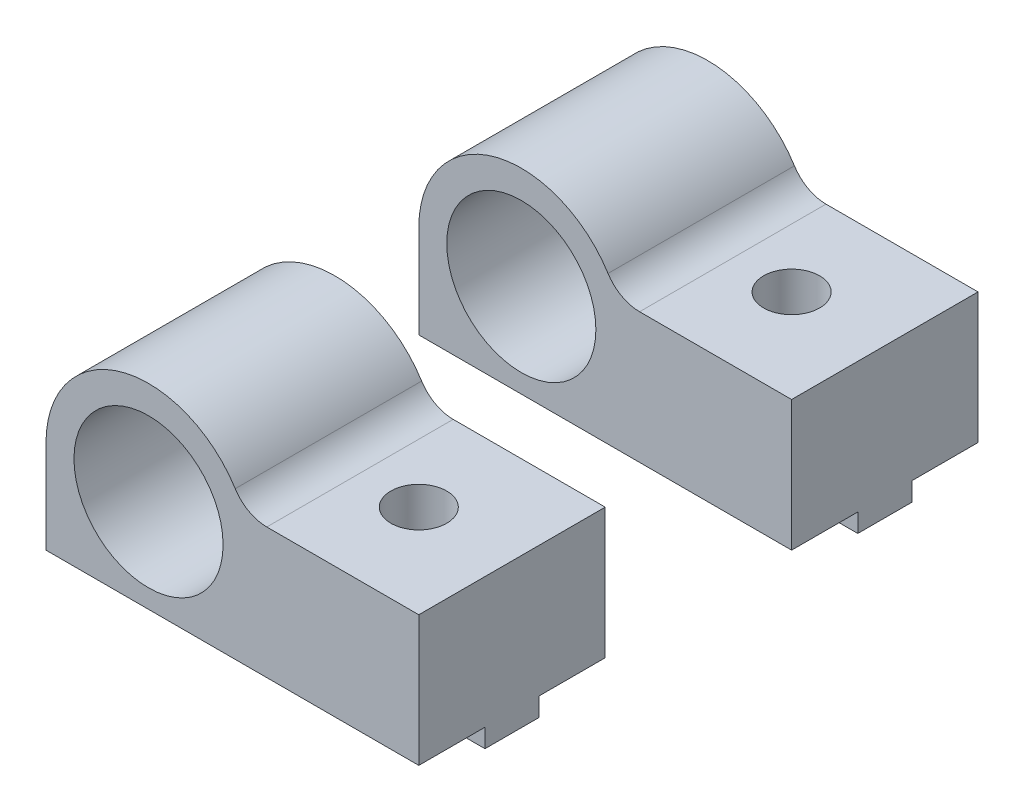
SolidWorks part; units mm, degrees
ref_plane "Front Plane" through (0, 0, 0) normal (0, 0, 1) x (1, 0, 0)
ref_plane "Top Plane" through (0, 0, 0) normal (0, 1, 0) x (1, 0, 0)
ref_plane "Right Plane" through (0, 0, 0) normal (1, 0, 0) x (0, 0, -1)
sketch "Sketch1" plane through (0, 0, 0) normal (0, 0, 1) x (1, 0, 0)
  line L0 (-5.5, 0) -> (-5.5, -5)
  line L1 (14.5, -5) -> (14.5, 2)
  line L3 (-5.5, -5) -> (14.5, -5)
  line L4 (14.5, 2) -> (5.1235, 2)
  arc A0 (-5.5, 0) -> (5.1235, 2) centre (0, 0) cw
  circle A1 centre (0, 0) radius 4
  dimension "D1" = 8
  dimension "D2" = 5.5
  dimension "D3" = 5
  dimension "D4" = 7
  dimension "D5" = 20
  dimension "D6" = 9.3765
extrude "Main" add sketch "Sketch1" along normal blind 10
sketch "Sketch3" plane through (0, -5, 0) normal (0, -1, 0) x (-1, 0, 0)
  line L0 (5.5, -10) -> (5.5, 0) construction
  line L1 (5.5, -6.45) -> (-14.5, -6.45)
  line L2 (5.5, -6.45) -> (5.5, -3.55)
  line L3 (5.5, -3.55) -> (-14.5, -3.55)
  line L4 (-14.5, -6.45) -> (-14.5, -3.55)
  line L5 (-14.5, -10) -> (-14.5, 0) construction
  line L6 (5.5, 0) -> (-14.5, 0) construction
  dimension "D1" = 2.9
  dimension "D2" = 3.55
extrude "MakerBeamRectangularGuide" add sketch "Sketch3" along normal blind 1
sketch "Sketch4" plane through (0, 2, 0) normal (0, 1, 0) x (1, 0, 0)
  line L0 (14.5, -10) -> (5.1235, -10) construction
  line L1 (14.5, -10) -> (14.5, 0) construction
  circle A0 centre (9.5, -5) radius 1.5
  dimension "D1" = 3
  dimension "D2" = 5
  dimension "D3" = 5
extrude "MakerBeamFixHole" cut sketch "Sketch4" against normal through all
fillet "Fillet1" radius 2 1 edges at (5.1235, 2, 5)
pattern_linear "LPattern1" count 2 spacing 20 along (0, 0, -1) of bodies 103
